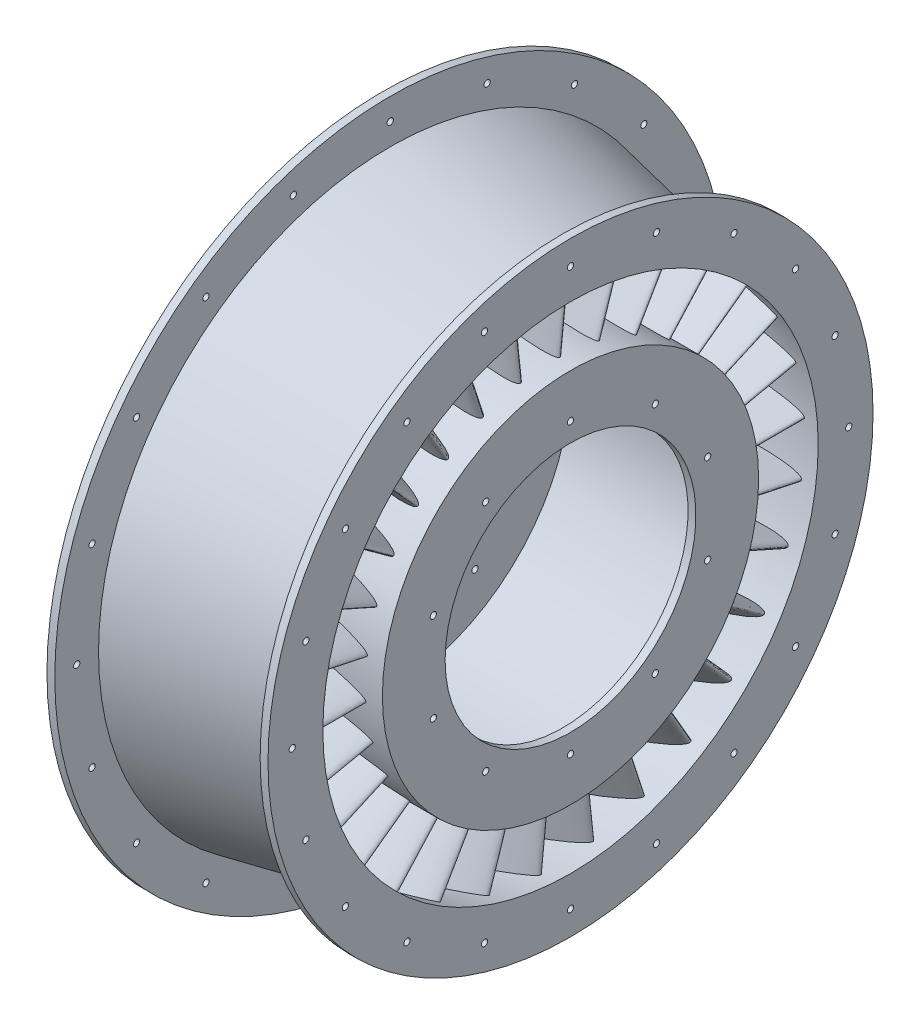
SolidWorks part; units mm, degrees
ref_plane "Front Plane" through (0, 0, 0) normal (0, 0, 1) x (1, 0, 0)
ref_plane "Top Plane" through (0, 0, 0) normal (0, 1, 0) x (1, 0, 0)
ref_plane "Right Plane" through (0, 0, 0) normal (1, 0, 0) x (0, 0, -1)
sketch "Sketch1" plane through (0, 0, 0) normal (0, 0, 1) x (1, 0, 0)
  line L0 (-164.8935, 0) -> (198.4867, 0) construction
  line L1 (60, 120) -> (60, 80)
  line L2 (60, 80) -> (55, 80)
  line L3 (55, 80) -> (55, 115)
  line L4 (55, 115) -> (-55, 115)
  line L5 (-55, 115) -> (-55, 80)
  line L6 (-55, 80) -> (-60, 80)
  line L7 (-60, 80) -> (-60, 120)
  line L8 (-60, 120) -> (60, 120)
  line L11 (60, 158) -> (-60, 182)
  line L12 (-60, 182) -> (-60, 214)
  line L13 (-60, 214) -> (-55, 214)
  line L14 (-55, 214) -> (-55, 186.099)
  line L15 (-55, 186.099) -> (55, 164.099)
  line L16 (55, 164.099) -> (55, 193)
  line L17 (55, 193) -> (60, 193)
  line L18 (60, 193) -> (60, 158)
  point P22 (0, 115)
  dimension "D2" = 5
  dimension "D3" = 110
  dimension "D4" = 5
  dimension "D5" = 5
  dimension "D6" = 120
  dimension "D7" = 5
  dimension "D8" = 193
  dimension "D9" = 120
  dimension "D10" = 182
  dimension "D11" = 214
  dimension "D12" = 158
  dimension "D13" = 5
  dimension "D14" = 5
  dimension "D15" = 80
  dimension "D16" = 80
revolve "Revolve1" add sketch "Sketch1" angle 360 about L0
sketch "Sketch2" plane through (0, 0, 0) normal (0, 0, 1) x (1, 0, 0)
  line L0 (-236.3814, 0) -> (317.036, 0) construction
  line L1 (0, 0) -> (49.2404, -8.6824) construction
  ellipse E0 centre (0, 0) end of major axis (-49.2404, 8.6824) minor radius 6
  dimension "D1" = 100
  dimension "D2" = 6
  dimension "D3" = 10
extrude "Boss-Extrude1" add sketch "Sketch2" along normal up to surface (64.6384 mm away) from offset 115 up to face at (60, 0, 158)
pattern_circular "CirPattern1" count 30 over 360 about axis through (-60, 0, 0) along (-1, 0, 0) of "Boss-Extrude1"
sketch "Sketch3" plane through (-60, 0, 0) normal (-1, 0, 0) x (0, 0, 1)
  circle A2 centre (0, 92) radius 2
  circle A3 centre (0, 200) radius 2
  circle A4 centre (61.8034, 190.2113) radius 2
  circle A6 centre (117.5571, 161.8034) radius 2
  circle A7 centre (54.0762, 74.4296) radius 2
  circle A8 centre (161.8034, 117.5571) radius 2
  circle A10 centre (190.2113, 61.8034) radius 2
  circle A11 centre (87.4972, 28.4296) radius 2
  circle A12 centre (200, 0) radius 2
  circle A14 centre (190.2113, -61.8034) radius 2
  circle A15 centre (87.4972, -28.4296) radius 2
  circle A16 centre (161.8034, -117.5571) radius 2
  circle A18 centre (117.5571, -161.8034) radius 2
  circle A19 centre (54.0762, -74.4296) radius 2
  circle A20 centre (61.8034, -190.2113) radius 2
  circle A22 centre (0, -200) radius 2
  circle A23 centre (0, -92) radius 2
  circle A24 centre (-61.8034, -190.2113) radius 2
  circle A26 centre (-117.5571, -161.8034) radius 2
  circle A27 centre (-54.0762, -74.4296) radius 2
  circle A28 centre (-161.8034, -117.5571) radius 2
  circle A30 centre (-190.2113, -61.8034) radius 2
  circle A31 centre (-87.4972, -28.4296) radius 2
  circle A32 centre (-200, 0) radius 2
  circle A34 centre (-190.2113, 61.8034) radius 2
  circle A35 centre (-87.4972, 28.4296) radius 2
  circle A36 centre (-161.8034, 117.5571) radius 2
  circle A38 centre (-117.5571, 161.8034) radius 2
  circle A39 centre (-54.0762, 74.4296) radius 2
  circle A40 centre (-61.8034, 190.2113) radius 2
  circle A42 centre (28.4296, 87.4972) radius 2 [skipped]
  circle A43 centre (74.4296, 54.0762) radius 2 [skipped]
  circle A44 centre (92, 0) radius 2 [skipped]
  circle A45 centre (74.4296, -54.0762) radius 2 [skipped]
  circle A46 centre (28.4296, -87.4972) radius 2 [skipped]
  circle A47 centre (-28.4296, -87.4972) radius 2 [skipped]
  circle A48 centre (-74.4296, -54.0762) radius 2 [skipped]
  circle A49 centre (-92, 0) radius 2 [skipped]
  circle A50 centre (-74.4296, 54.0762) radius 2 [skipped]
  circle A51 centre (-28.4296, 87.4972) radius 2 [skipped]
  point P4 (0, 0)
  point P5 (0, 0)
  point P85 (0, 0)
  dimension "D2" = 200
  dimension "D4" = 4
  dimension "D5" = 20
  dimension "D3" = 4
  dimension "D1" = 92
extrude "Cut-Extrude1" cut sketch "Sketch3" against normal through all
sketch "Sketch4" plane through (60, 0, 0) normal (1, 0, 0) x (0, 0, -1)
  circle A0 centre (0, 177.5) radius 2
  circle A1 centre (54.8505, 168.8125) radius 2
  circle A2 centre (104.3319, 143.6005) radius 2
  circle A3 centre (143.6005, 104.3319) radius 2
  circle A4 centre (168.8125, 54.8505) radius 2
  circle A5 centre (177.5, 0) radius 2
  circle A6 centre (168.8125, -54.8505) radius 2
  circle A7 centre (143.6005, -104.3319) radius 2
  circle A8 centre (104.3319, -143.6005) radius 2
  circle A9 centre (54.8505, -168.8125) radius 2
  circle A10 centre (0, -177.5) radius 2
  circle A11 centre (-54.8505, -168.8125) radius 2
  circle A12 centre (-104.3319, -143.6005) radius 2
  circle A13 centre (-143.6005, -104.3319) radius 2
  circle A14 centre (-168.8125, -54.8505) radius 2
  circle A15 centre (-177.5, 0) radius 2
  circle A16 centre (-168.8125, 54.8505) radius 2
  circle A17 centre (-143.6005, 104.3319) radius 2
  circle A18 centre (-104.3319, 143.6005) radius 2
  circle A19 centre (-54.8505, 168.8125) radius 2
  point P44 (0, 0)
  dimension "D1" = 4
  dimension "D2" = 177.5
  dimension "D3" = 20
extrude "Cut-Extrude2" cut sketch "Sketch4" against normal blind 5
